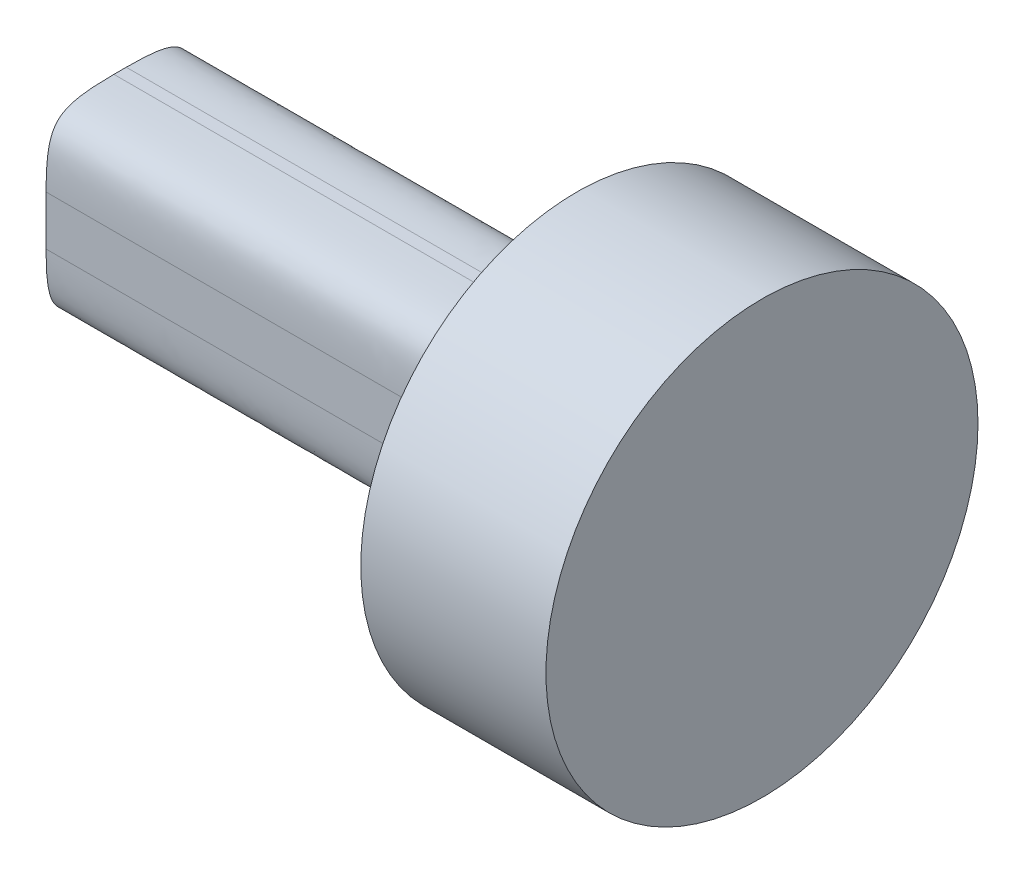
SolidWorks part; units mm, degrees
ref_plane "Front Plane" through (0, 0, 0) normal (0, 0, 1) x (1, 0, 0)
ref_plane "Top Plane" through (0, 0, 0) normal (0, 1, 0) x (1, 0, 0)
ref_plane "Right Plane" through (0, 0, 0) normal (1, 0, 0) x (0, 0, -1)
sketch "Sketch2" plane through (0, 0, 0) normal (0, 0, 1) x (1, 0, 0)
  line L1 (-184.4726, 79.7965) -> (-147.4726, 79.7965)
  line L2 (-184.4726, 79.7965) -> (-184.4726, 64.7965)
  line L3 (-184.4726, 64.7965) -> (-147.4726, 64.7965)
  line L4 (-147.4726, 79.7965) -> (-147.4726, 64.7965)
  dimension "D1" = 37
  dimension "D2" = 15
extrude "Boss-Extrude1" add sketch "Sketch2" along normal blind 12
ref_plane "Plane1" through (-147.4726, 0, 0) normal (1, 0, 0) x (0, 0, -1)
sketch "Sketch3" plane through (-147.4726, 0, 0) normal (1, 0, 0) x (0, 0, -1)
  line L0 (-12, 79.7965) -> (0, 79.7965) construction
  line L1 (-12, 64.7965) -> (-12, 79.7965) construction
  circle A0 centre (-6, 72.2965) radius 17.5
  point P4 (-6, 79.7965)
  point P7 (-12, 72.2965)
  dimension "D1" = 35
extrude "Boss-Extrude2" add sketch "Sketch3" along normal blind 15
fillet "Fillet1" radius 5.5 4 edges at (-165.9726, 64.7965, 0) (-165.9726, 64.7965, 12) (-165.9726, 79.7965, 0) (-165.9726, 79.7965, 12)
